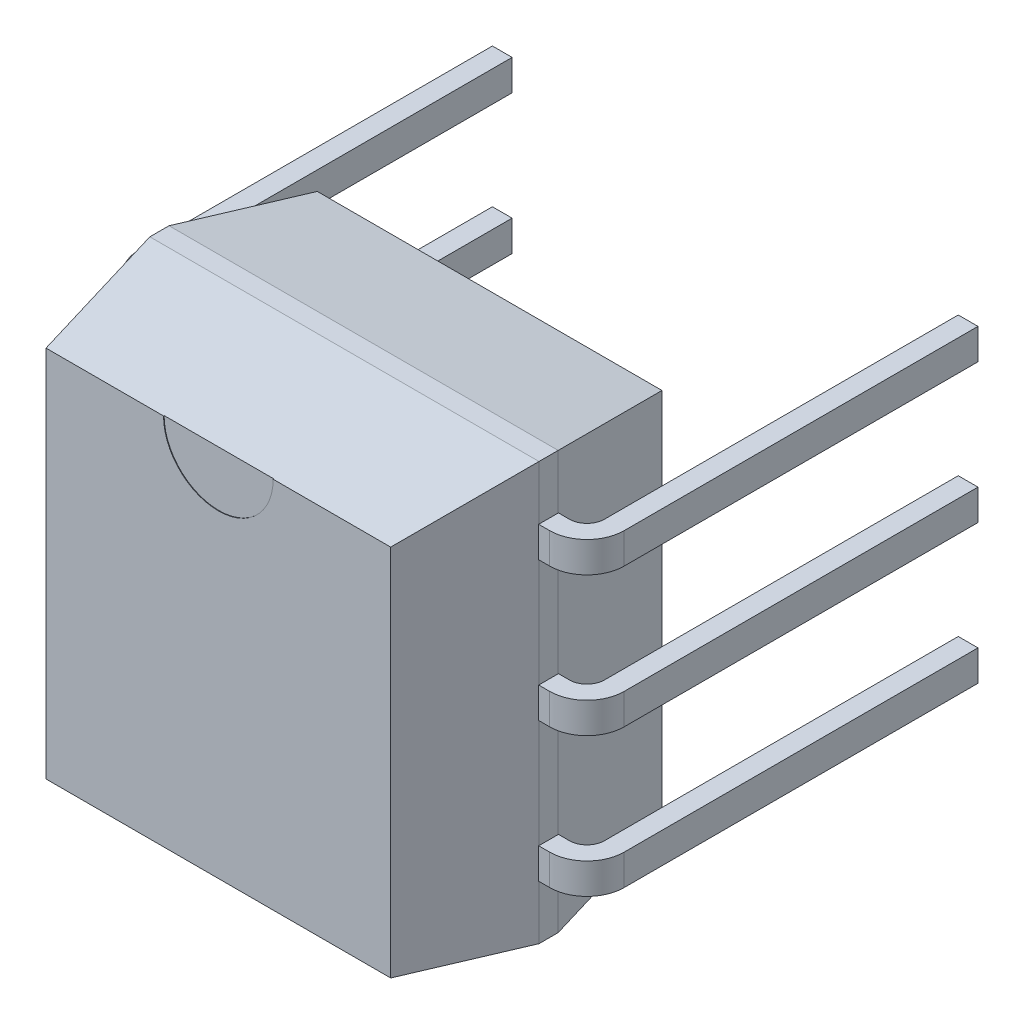
SolidWorks part; units mm, degrees
note: The reader was unsure of these and kept them because the rebuilt part matched: shared geometry of "Эскиз5<2>".
ref_plane "Front" through (0, 0, 0) normal (0, 0, 1) x (1, 0, 0)
ref_plane "Top" through (0, 0, 0) normal (0, 1, 0) x (1, 0, 0)
ref_plane "Right" through (0, 0, 0) normal (1, 0, 0) x (0, 0, -1)
sketch "Эскиз1" plane through (0, 0, 0) normal (0, 0, 1) x (1, 0, 0)
  line L1 (-0.8, -8.42) -> (0.8, -8.42)
  line L2 (-0.8, -8.42) -> (-0.8, -6.82)
  line L3 (-0.8, -6.82) -> (0.8, -6.82)
  line L4 (0.8, -8.42) -> (0.8, -6.82)
  line L5 (-0.8, -5.88) -> (0.8, -5.88)
  line L6 (-0.8, -5.88) -> (-0.8, -4.28)
  line L7 (-0.8, -4.28) -> (0.8, -4.28)
  line L8 (0.8, -5.88) -> (0.8, -4.28)
  line L9 (-0.8, -3.34) -> (0.8, -3.34)
  line L10 (-0.8, -3.34) -> (-0.8, -1.74)
  line L11 (-0.8, -1.74) -> (0.8, -1.74)
  line L12 (0.8, -3.34) -> (0.8, -1.74)
  line L13 (-0.8, -0.8) -> (0.8, -0.8)
  line L14 (-0.8, -0.8) -> (-0.8, 0.8)
  line L15 (-0.8, 0.8) -> (0.8, 0.8)
  line L16 (0.8, -0.8) -> (0.8, 0.8)
  line L17 (7.7, -8.42) -> (9.3, -8.42)
  line L18 (7.7, -8.42) -> (7.7, -6.82)
  line L19 (7.7, -6.82) -> (9.3, -6.82)
  line L20 (9.3, -8.42) -> (9.3, -6.82)
  line L21 (7.7, -5.88) -> (9.3, -5.88)
  line L22 (7.7, -5.88) -> (7.7, -4.28)
  line L23 (7.7, -4.28) -> (9.3, -4.28)
  line L24 (9.3, -5.88) -> (9.3, -4.28)
  line L25 (7.7, -3.34) -> (9.3, -3.34)
  line L26 (7.7, -3.34) -> (7.7, -1.74)
  line L27 (7.7, -1.74) -> (9.3, -1.74)
  line L28 (9.3, -3.34) -> (9.3, -1.74)
  line L29 (7.7, -0.8) -> (9.3, -0.8)
  line L30 (7.7, -0.8) -> (7.7, 0.8)
  line L31 (7.7, 0.8) -> (9.3, 0.8)
  line L32 (9.3, -0.8) -> (9.3, 0.8)
ref_plane "Плоскость1" through (0, 0, 5.33) normal (0, 0, 1) x (1, 0, 0)
sketch "Эскиз3" plane through (0, 0, 5.33) normal (0, 0, 1) x (1, 0, 0)
  line L0 (0.7, 1.27) -> (4.25, 1.27)
  line L1 (4.25, 1.27) -> (7.8, 1.27)
  line L2 (0.7, -8.89) -> (0.7, 1.27)
  line L3 (7.8, 1.27) -> (7.8, -8.89)
  line L4 (7.8, -8.89) -> (0.7, -8.89)
  line L5 (4.25, -8.89) -> (4.25, 1.27) construction
  dimension "D1" = 10.16
  dimension "D2" = 7.1
  dimension "D3" = 0.7
  dimension "D4" = 8.89
extrude "Вытянуть1" add sketch "Эскиз3" against normal blind 4.95
sketch "Эскиз4" plane through (0, 0, 0) normal (0, 1, 0) x (1, 0, 0)
  line L0 (0, 0) -> (0, -2.355)
  line L1 (0.5, -2.855) -> (0.7, -2.855)
  line L2 (0.7, -0.38) -> (0.7, -5.33) construction
  line L3 (4.25, -0.38) -> (4.25, -5.33) construction
  line L4 (7.8, -0.38) -> (0.7, -0.38) construction
  line L5 (7.8, -5.33) -> (0.7, -5.33) construction
  line L6 (8, -2.855) -> (7.8, -2.855)
  line L7 (8.5, 0) -> (8.5, -2.355)
  line L8 (0.7, -2.855) -> (7.8, -2.855)
  line L9 (8.5, 0) -> (8.5, 4.1)
  arc A0 (0, -2.355) -> (0.5, -2.855) centre (0.5, -2.355) ccw
  arc A1 (8, -2.855) -> (8.5, -2.355) centre (8, -2.355) ccw
  point P18 (0, -2.855)
  point P21 (8.5, -2.855)
  dimension "D2" = 0.5
  dimension "D1" = 4.1
sketch "Эскиз5" plane through (0, 0, 0) normal (0, 0, 1) x (1, 0, 0)
  line L0 (0.18, -2.26) -> (-0.18, -2.26)
  line L1 (0.18, 0.28) -> (-0.18, 0.28)
  line L2 (0.18, 0.28) -> (0.18, -0.28)
  line L3 (0.18, -0.28) -> (-0.18, -0.28)
  line L4 (-0.18, 0.28) -> (-0.18, -0.28)
  line L5 (0.18, -2.26) -> (0.18, -2.82)
  line L6 (0.18, -2.82) -> (-0.18, -2.82)
  line L7 (-0.18, -2.26) -> (-0.18, -2.82)
  line L8 (0.18, -4.8) -> (-0.18, -4.8)
  line L9 (0.18, -4.8) -> (0.18, -5.36)
  line L10 (0.18, -5.36) -> (-0.18, -5.36)
  line L11 (-0.18, -4.8) -> (-0.18, -5.36)
  line L12 (0.18, -7.34) -> (-0.18, -7.34)
  line L13 (0.18, -7.34) -> (0.18, -7.9)
  line L14 (0.18, -7.9) -> (-0.18, -7.9)
  line L15 (-0.18, -7.34) -> (-0.18, -7.9)
  dimension "D1" = 0.36
  dimension "D2" = 0.18
  dimension "D3" = 0.28
  dimension "D4" = 0.56
  dimension "D5" = 2.54
sweep "По траектории1" add profiles "Эскиз5" path "Эскиз4"
extrude "Вытянуть2" add sketch "Эскиз5<2>" against normal blind 4.1
sketch "Эскиз5<2>" plane through (0, 0, 0) normal (0, 0, 1) x (1, 0, 0) same geometry as "Эскиз5"
chamfer "Фаска1" distance 2.3 angle 10 8 edges at (4.25, -8.89, 0.38) (7.8, -3.81, 0.38) (4.25, 1.27, 0.38) (0.7, -3.81, 0.38) (4.25, 1.27, 5.33) (7.8, -3.81, 5.33) (4.25, -8.89, 5.33) (0.7, -3.81, 5.33)
sketch "Эскиз6" plane through (0, 0, 5.33) normal (0, 0, 1) x (1, 0, 0)
  line L0 (7.3944, 0.8644) -> (1.1056, 0.8644) construction
  circle A0 centre (4.25, 0.8644) radius 1
  dimension "D1" = 2
extrude "Вырез-Вытянуть1" cut sketch "Эскиз6" against normal blind 0.01
sketch "Эскиз7" plane through (0, 0, 5.33) normal (0, 0, 1) x (1, 0, 0)
  line L0 (7.8, -8.89) -> (0.7, -8.89) construction
  line L1 (-1.1745, -10.0023) -> (9.3817, -10.0023)
  line L2 (-1.1745, -10.0023) -> (-1.1745, -6.35)
  line L3 (-1.1745, -6.35) -> (9.3817, -6.35)
  line L4 (9.3817, -10.0023) -> (9.3817, -6.35)
  dimension "D1" = 2.54
extrude "Вырез-Вытянуть2" cut sketch "Эскиз7" against normal blind 20
chamfer "Фаска2" distance 2.3 angle 10 2 edges at (4.25, -6.35, 0.38) (4.25, -6.35, 5.33)
